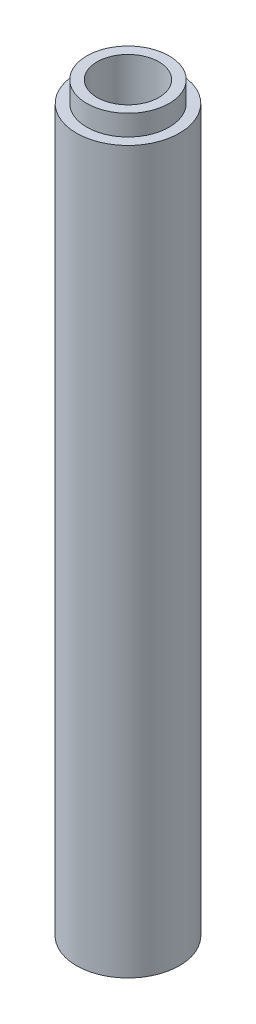
SolidWorks part; units mm, degrees
ref_plane "Front Plane" through (0, 0, 0) normal (0, 0, 1) x (1, 0, 0)
ref_plane "Top Plane" through (0, 0, 0) normal (0, 1, 0) x (1, 0, 0)
ref_plane "Right Plane" through (0, 0, 0) normal (1, 0, 0) x (0, 0, -1)
sketch "Sketch1" plane through (0, 0, 0) normal (0, 1, 0) x (1, 0, 0)
  circle A0 centre (0, 0) radius 12.7
  dimension "D1" = 25.4
extrude "Boss-Extrude1" add sketch "Sketch1" along normal blind 177.8
sketch "Sketch4" plane through (0, 177.8, 0) normal (0, 1, 0) x (1, 0, 0)
  circle A2 centre (0, 0) radius 10.16
  circle A3 centre (0, 0) radius 10.16
  dimension "D1" = 2.54
extrude "Boss-Extrude2" add sketch "Sketch4" along normal blind 5.08
sketch "Sketch5" plane through (0, 182.88, 0) normal (0, 1, 0) x (1, 0, 0)
  circle A0 centre (0, 0) radius 10.16 construction
  circle A1 centre (0, 0) radius 10.16 construction
  circle A2 centre (0, 0) radius 7.62
  dimension "D1" = 2.54
extrude "Cut-Extrude1" cut sketch "Sketch5" against normal through all
